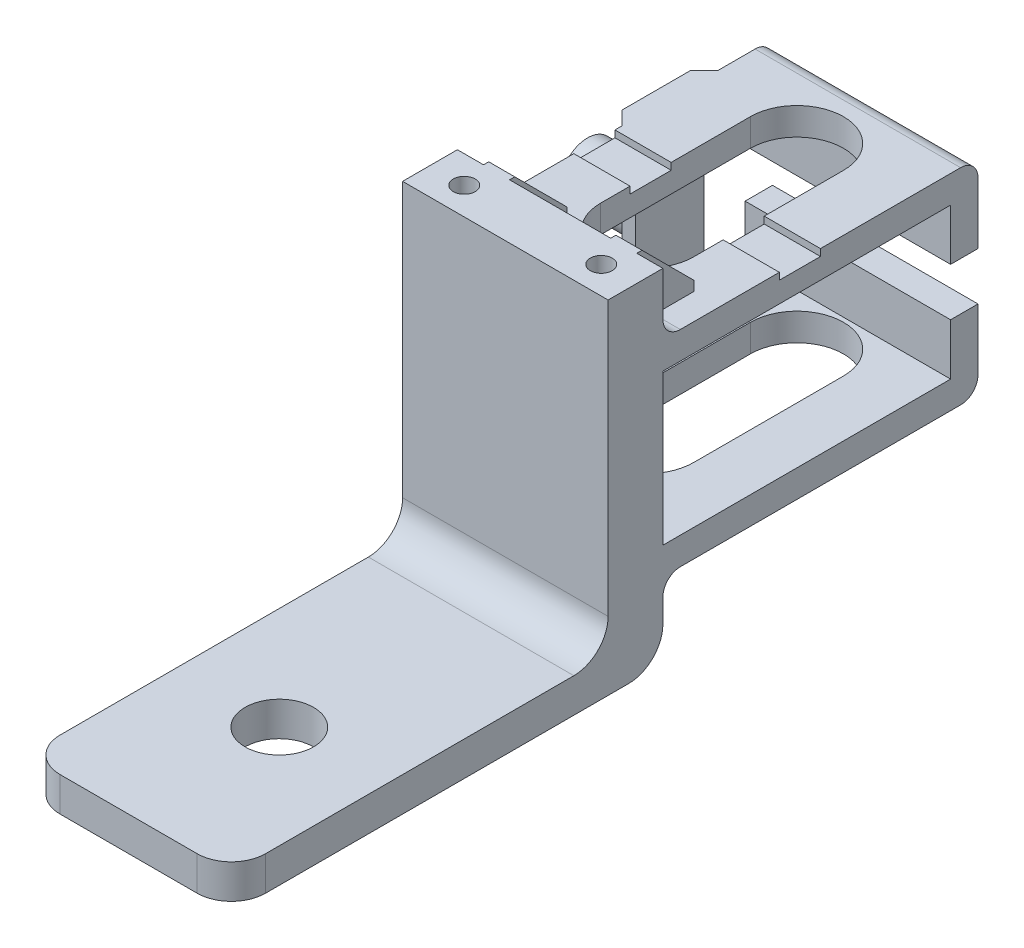
SolidWorks part; units mm, degrees
ref_plane "Front Plane" through (0, 0, 0) normal (0, 0, 1) x (1, 0, 0)
ref_plane "Top Plane" through (0, 0, 0) normal (0, 1, 0) x (1, 0, 0)
ref_plane "Right Plane" through (0, 0, 0) normal (1, 0, 0) x (0, 0, -1)
sketch "Sketch1" plane through (0, 0, 0) normal (1, 0, 0) x (0, 0, -1)
  line L1 (0, 0) -> (63, 0)
  line L2 (0, 0) -> (0, 5)
  line L3 (0, 5) -> (63, 5)
  line L4 (63, 0) -> (63, 5)
  dimension "D1" = 5
  dimension "D2" = 63
extrude "Boss-Extrude1" add sketch "Sketch1" along normal blind 30 contours L3 L4 L1 L2
sketch "Sketch2" plane through (0, 5, 0) normal (0, 1, 0) x (1, 0, 0)
  line L0 (30, 0) -> (30, 63) construction
  line L1 (0, 63) -> (30, 63)
  line L2 (0, 63) -> (0, 55)
  line L3 (0, 55) -> (30, 55)
  line L4 (30, 63) -> (30, 55)
  dimension "D1" = 8
extrude "Boss-Extrude2" add sketch "Sketch2" along normal blind 45
sketch "Sketch3" plane through (0, 5, 0) normal (0, 1, 0) x (1, 0, 0)
  line L0 (30, 0) -> (0, 0) construction
  circle A0 centre (15, 22) radius 5
  point P4 (15, 0)
  dimension "D2" = 10
  dimension "D1" = 22
extrude "Cut-Extrude1" cut sketch "Sketch3" against normal through all
sketch "Sketch5" plane through (0, 50, 0) normal (0, 1, 0) x (1, 0, 0)
  line L0 (0, 63) -> (0, 55) construction
  line L1 (30, 55) -> (30, 63) construction
  circle A0 centre (5, 59) radius 1.6
  circle A1 centre (25, 59) radius 1.6
  point P5 (0, 59)
  dimension "D1" = 3.2
  dimension "D3" = 5
  dimension "D2" = 5
extrude "Cut-Extrude3" cut sketch "Sketch5" against normal blind 14
fillet "Fillet1" radius 5 4 edges at (15, 0, -63) (15, 5, -55) (30, 2.5, 0) (0, 2.5, 0)
sketch "Sketch6" plane through (30, 0, 0) normal (1, 0, 0) x (0, 0, -1)
  line L0 (63, 5) -> (63, 50) construction
  line L1 (63, 37) -> (105, 37)
  line L2 (63, 37) -> (63, 15)
  line L3 (63, 15) -> (105, 15)
  line L4 (105, 37) -> (105, 15)
  line L5 (5, 0) -> (58, 0) construction
  line L6 (63, 41) -> (109, 41)
  line L7 (63, 41) -> (63, 11)
  line L8 (63, 11) -> (109, 11)
  line L9 (109, 41) -> (109, 11)
  line M11 (63, 5) -> (63, 50)
  dimension "D1" = 4
  dimension "D2" = 4
  dimension "D3" = 4
  dimension "D4" = 22
  dimension "D5" = 42
  dimension "D6" = 15
extrude "Boss-Extrude3" add sketch "Sketch6" against normal up to surface (30 mm away) contours L9 L6 L1 L4 L3 L8 M11 region at (30, 39, -63.5492) up to face at (0, 15.3661, -44.5089)
fillet "Fillet2" radius 2.54 4 edges at (15, 11, -109) (15, 11, -63) (15, 41, -63) (15, 41, -109)
sketch "Sketch8" plane through (0, 41, 0) normal (0, 1, 0) x (1, 0, 0)
  line L0 (15, 97.57) -> (15, 75.7) construction
  line L1 (21.7934, 97.57) -> (21.7934, 75.7)
  line L2 (8.2066, 97.57) -> (8.2066, 75.7)
  line L3 (0, 65.54) -> (30, 65.54) construction
  line L4 (30, 106.46) -> (0, 106.46) construction
  arc A0 (21.7934, 97.57) -> (8.2066, 97.57) centre (15, 97.57) ccw
  arc A1 (8.2066, 75.7) -> (21.7934, 75.7) centre (15, 75.7) ccw
  point P2 (15, 86.635)
  point P7 (15, 65.54)
  dimension "D1" = 8.89
  dimension "D2" = 10.16
extrude "Cut-Extrude5" cut sketch "Sketch8" against normal through all
sketch "Sketch9" plane through (0, 41, 0) normal (0, 1, 0) x (1, 0, 0)
  line L0 (30, 63) -> (0, 63) construction
  line L1 (3.81, 63) -> (7.62, 63)
  line L2 (3.81, 63) -> (3.81, 71.3781)
  line L3 (3.81, 71.3781) -> (7.62, 71.3781)
  line L4 (7.62, 63) -> (7.62, 71.3781)
  line L6 (22.38, 63) -> (26.19, 63)
  line L7 (22.38, 63) -> (22.38, 71.3781)
  line L8 (22.38, 71.3781) -> (26.19, 71.3781)
  line L9 (26.19, 63) -> (26.19, 71.3781)
  line L10 (30, 65.54) -> (30, 106.46) construction
  dimension "D1" = 3.81
  dimension "D3" = 3.81
extrude "Boss-Extrude4" add sketch "Sketch9" along normal up to surface (9 mm away) up to face at (5, 50, -57.4)
chamfer "Chamfer1" distance 7.62 angle 45 2 edges at (5.715, 50, -71.3781) (24.285, 50, -71.3781)
sketch "Sketch10" plane through (0, 11, 0) normal (0, -1, 0) x (1, 0, 0)
  line L1 (3.81, -63) -> (7.62, -63)
  line L2 (3.81, -63) -> (3.81, -71.3781)
  line L3 (3.81, -71.3781) -> (7.62, -71.3781)
  line L4 (7.62, -63) -> (7.62, -71.3781)
  line L5 (22.38, -63) -> (26.19, -63)
  line L6 (22.38, -63) -> (22.38, -71.3781)
  line L7 (22.38, -71.3781) -> (26.19, -71.3781)
  line L8 (26.19, -63) -> (26.19, -71.3781)
extrude "Boss-Extrude5" add sketch "Sketch10" along normal up to vertex (6 mm away) up to point (30, 5, -63)
chamfer "Chamfer2" distance 7.62 angle 45 2 edges at (24.285, 5, -71.3781) (5.715, 5, -71.3781)
ref_plane "Plane2" through (15, 0, 0) normal (1, 0, 0) x (0, 0, -1)
sketch "Sketch11" plane through (30, 0, 0) normal (1, 0, 0) x (0, 0, -1)
  line L0 (105, 37) -> (105, 15) construction
  line L1 (105, 29.5) -> (109, 29.5)
  line L2 (105, 29.5) -> (105, 22.5)
  line L3 (105, 22.5) -> (109, 22.5)
  line L4 (109, 29.5) -> (109, 22.5)
  line L5 (109, 38.46) -> (109, 13.54) construction
  point P8 (109, 26)
  point P9 (109, 26)
  dimension "D1" = 7
extrude "Cut-Extrude6" cut sketch "Sketch11" against normal through all
sketch "Sketch13" plane through (0, 0, 0) normal (-1, 0, 0) x (0, 0, 1)
  line L0 (-65.54, 41) -> (-106.46, 41) construction
  line L1 (-99, 41) -> (-89, 41)
  line L2 (-99, 41) -> (-99, 11)
  line L3 (-99, 11) -> (-89, 11)
  line L4 (-89, 41) -> (-89, 11)
  line L5 (-65.54, 11) -> (-106.46, 11) construction
  line L6 (-109, 38.46) -> (-109, 29.5) construction
  point P8 (-94, 41)
  dimension "D1" = 15
  dimension "D2" = 10
extrude "Boss-Extrude6" add sketch "Sketch13" along normal blind 2 contours L2 L3 L4 L1
sketch "Sketch14" plane through (-2, 0, 0) normal (-1, 0, 0) x (0, 0, 1)
  line L0 (-99, 41) -> (-99, 11) construction
  line L1 (-99, 41) -> (-89, 41) construction
  circle A0 centre (-94, 26) radius 4
  point P2 (-99, 26)
  point P3 (-94, 41)
  point P6 (0, 0)
  point P9 (0, 0)
  dimension "D1" = 8
extrude "Boss-Extrude7" add sketch "Sketch14" along normal blind 10
chamfer "Chamfer3" distance 2 angle 45 4 edges at (0, 13, -89) (0, 39, -89) (0, 13, -99) (0, 39, -99)
sketch "Sketch15" plane through (0, 41, 0) normal (0, 1, 0) x (1, 0, 0)
  line L0 (0, 65.54) -> (0, 87) construction
  line L1 (0, 86) -> (30, 86)
  line L2 (0, 86) -> (0, 80)
  line L3 (0, 80) -> (30, 80)
  line L4 (30, 86) -> (30, 80)
  line L5 (30, 65.54) -> (30, 106.46) construction
  line L6 (0, 109) -> (30, 109) construction
  dimension "D1" = 6
  dimension "D2" = 23
extrude "Cut-Extrude7" cut sketch "Sketch15" against normal blind 1
